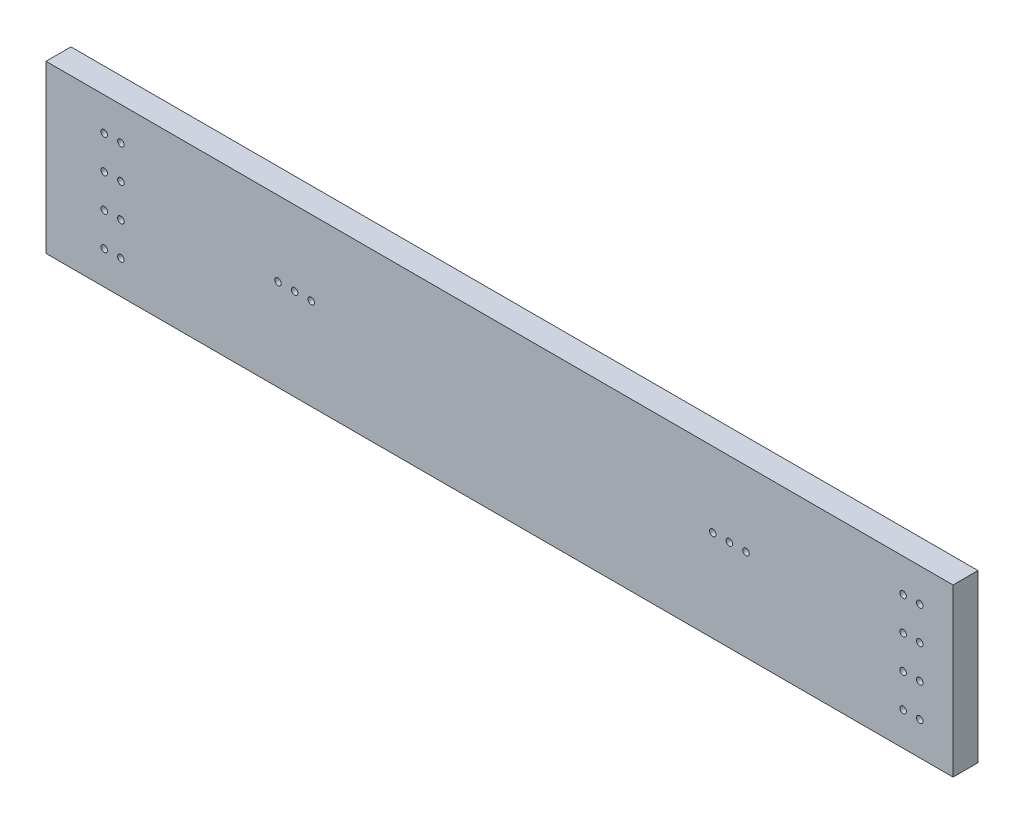
SolidWorks part; units mm, degrees
material "Pine"
ref_plane "Front Plane" through (0, 0, 0) normal (0, 0, 1) x (1, 0, 0)
ref_plane "Top Plane" through (0, 0, 0) normal (0, 1, 0) x (1, 0, 0)
ref_plane "Right Plane" through (0, 0, 0) normal (1, 0, 0) x (0, 0, -1)
sketch "robot, section, top of tube" plane through (0, 0, 0) normal (0, 1, 0) x (1, 0, 0)
  line L1 (-330.2, 0) -> (330.2, 0)
  line L2 (-330.2, 0) -> (-330.2, 660.4)
  line L3 (-330.2, 660.4) -> (330.2, 660.4)
  line L4 (330.2, 0) -> (330.2, 660.4)
  line L6 (146.05, 0) -> (146.05, 45.2974)
  line L7 (-146.05, 0) -> (-146.05, 45.2974)
  line L8 (0, 0) -> (0, 660.4) construction
  dimension "D1" = 660.4
  dimension "D3" = 184.15
sketch "robot approx side" plane through (0, 0, 0) normal (0, 0, 1) x (1, 0, 0)
  line L0 (-146.812, 0) -> (-146.812, 25.4)
  line L1 (-330.2, 0) -> (330.2, 0) construction
  line L2 (-146.812, 2.6416) -> (-121.9604, 2.6416)
  line L4 (0, 0) -> (0, 48.6273) construction
  line L5 (146.812, 2.6416) -> (121.9604, 2.6416)
  line L6 (146.812, 0) -> (146.812, 25.4)
  dimension "D1" = 2.6416
  dimension "D2" = 25.4
  dimension "D3" = 183.388
ref_plane "floor" through (0, -93.726, 0) normal (0, 1, 0) x (1, 0, 0)
ref_plane "bottom" through (0, -57.15, 0) normal (0, 1, 0) x (1, 0, 0)
ref_plane "top" through (0, 69.85, 0) normal (0, 1, 0) x (1, 0, 0)
sketch "Sketch4" plane through (0, 0, 0) normal (0, 1, 0) x (1, 0, 0)
  line L0 (-330.2, 0) -> (330.2, 0) construction
  line L1 (336.55, -6.35) -> (-355.6, -6.35)
  line L2 (336.55, -6.35) -> (336.55, -25.4)
  line L3 (336.55, -25.4) -> (-355.6, -25.4)
  line L4 (-355.6, -6.35) -> (-355.6, -25.4)
  line L5 (330.2, 0) -> (330.2, 660.4) construction
  line L6 (-330.2, 0) -> (-330.2, 660.4) construction
  dimension "D1" = 19.05
  dimension "D2" = 6.35
  dimension "D3" = 6.35
  dimension "D4" = 25.4
extrude "Boss-Extrude1" add sketch "Sketch4" along normal up to surface (69.85 mm away) from surface up to plane "top" starting at plane "bottom"
sketch "Sketch5" plane through (0, 0, 25.4) normal (0, 0, 1) x (1, 0, 0)
  line L0 (-9.525, 69.85) -> (-9.525, -57.15) construction
  line L1 (146.812, 0) -> (146.812, 25.4) construction
  line L2 (-355.6, 69.85) -> (-355.6, -57.15) construction
  line L4 (-355.6, 69.85) -> (336.55, 69.85) construction
  line L5 (-355.6, -57.15) -> (336.55, -57.15) construction
  line L6 (-355.6, 12.7) -> (336.55, 12.7) construction
  line L7 (336.55, 69.85) -> (336.55, -57.15) construction
  line L8 (-146.812, 0) -> (-146.812, 25.4) construction
  circle A0 centre (-311.15, 44.45) radius 2.4955
  circle A1 centre (-298.45, 44.45) radius 2.4955
  circle A2 centre (-311.15, 19.05) radius 2.4955
  circle A3 centre (-298.45, 19.05) radius 2.4955
  circle A4 centre (-311.15, -6.35) radius 2.4955
  circle A5 centre (-298.45, -6.35) radius 2.4955
  circle A6 centre (-311.15, -31.75) radius 2.4955
  circle A7 centre (-298.45, -31.75) radius 2.4955
  circle A14 centre (298.45, 44.45) radius 2.4955
  circle A15 centre (311.15, 44.45) radius 2.4955
  circle A16 centre (-178.562, 12.7) radius 2.4892
  circle A17 centre (-165.862, 12.7) radius 2.4892
  circle A18 centre (-153.162, 12.7) radius 2.4892
  circle A19 centre (153.162, 12.7) radius 2.4892
  circle A20 centre (165.862, 12.7) radius 2.4892
  circle A21 centre (178.562, 12.7) radius 2.4892
  circle A22 centre (311.15, 19.05) radius 2.4955
  circle A23 centre (298.45, 19.05) radius 2.4955
  circle A24 centre (311.15, -6.35) radius 2.4955
  circle A25 centre (298.45, -6.35) radius 2.4955
  circle A26 centre (311.15, -31.75) radius 2.4955
  circle A27 centre (298.45, -31.75) radius 2.4955
  point P30 (-146.812, 12.7)
  dimension "D3" = 4.9911
  dimension "D1" = 4.9784
  dimension "D9" = 12.7
  dimension "D10" = 6.35
  dimension "D11" = 6.35
  dimension "D12" = 12.7
  dimension "D13" = 12.7
  dimension "D16" = 25.4
  dimension "D2" = 12.7
  dimension "D4" = 25.4
  dimension "D5" = 44.45
  dimension "D7" = 25.4
  dimension "D8" = 12.7
  dimension "D14" = 25.4
  dimension "D15" = 12.7
  dimension "D18" = 25.4
  dimension "D6" = 4
  dimension "D17" = 4
extrude "Cut-Extrude1" cut sketch "Sketch5" against normal through all
